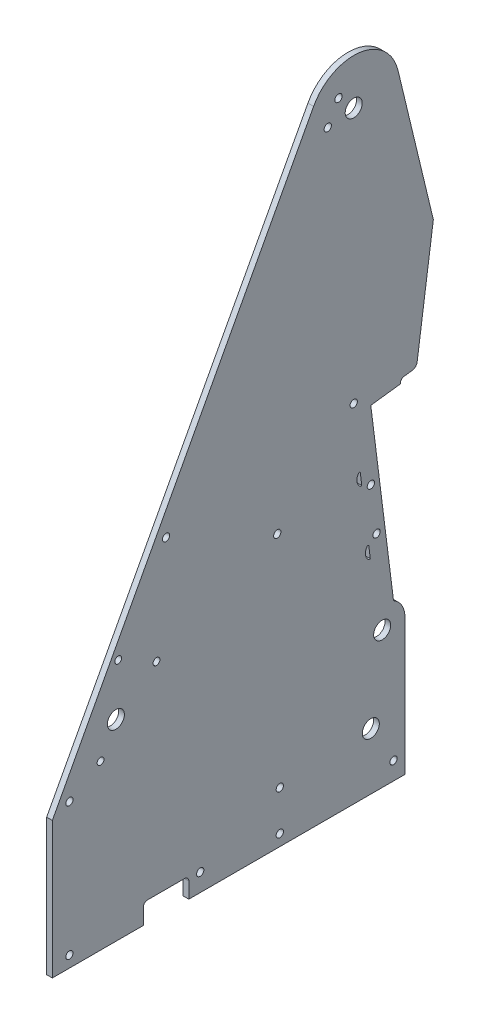
SolidWorks part; units mm, degrees
ref_plane "Front Plane" through (0, 0, 0) normal (0, 0, 1) x (1, 0, 0)
ref_plane "Top Plane" through (0, 0, 0) normal (0, 1, 0) x (1, 0, 0)
ref_plane "Right Plane" through (0, 0, 0) normal (1, 0, 0) x (0, 0, -1)
sketch "Sketch1" plane through (0, 0, 0) normal (1, 0, 0) x (0, 0, -1)
  line L0 (0, 0) -> (0, 76.2)
  line L6 (-19.05, 188.0016) -> (-2.512, 190.0852)
  line L7 (6.4943, 193.62) -> (15.875, 260.35)
  line L8 (15.875, 260.35) -> (-3.8791, 342.4892)
  line L9 (-50.965, 348.5436) -> (-196.85, 76.2)
  line L10 (-196.85, 0) -> (0, 0)
  line L11 (-196.85, 76.2) -> (-196.85, 0)
  line L12 (-19.05, 188.0016) -> (-6.35, 87.1985)
  line L13 (-0.4471, 192.7455) -> (6.4943, 193.62)
  line L14 (-2.512, 190.0852) -> (-3.1086, 194.8203) construction
  line L15 (-2.512, 190.0852) -> (6.1508, 191.1766) construction
  line L16 (6.1508, 191.1766) -> (6.4943, 193.62) construction
  arc A0 (-3.8791, 342.4892) -> (-50.965, 348.5436) centre (-28.575, 336.55) ccw
  arc A3 (0, 76.2) -> (-6.35, 87.1985) centre (-12.7, 76.2) ccw
  arc A4 (-2.512, 190.0852) -> (-0.4471, 192.7455) centre (-0.1494, 190.3829) cw
  dimension "D2" = 25.4
  dimension "D6" = 196.85
  dimension "D7" = 76.2
  dimension "D12" = 12.7
  dimension "D8" = 19.05
  dimension "D10" = 2.3813
  dimension "D1" = 28.575
  dimension "D3" = 336.55
  dimension "D4" = 25.4
  dimension "D5" = 101.6
  dimension "D9" = 6.35
  dimension ".5" = 12.7
  dimension "D11" = 76.2
  dimension "D13" = 76.2
  dimension "D14" = 15.875
  dimension "D15" = 6.35
extrude "Boss-Extrude1" add sketch "Sketch1" along normal blind 3.175
sketch "Sketch2" plane through (3.175, 0, 0) normal (1, 0, 0) x (0, 0, -1)
  line L16 (-146.05, 8.7909) -> (-146.05, -0.3034) construction
  line L17 (-123.0376, 11.1785) -> (-143.6624, 11.1785) construction
  line L18 (-120.65, -0.3034) -> (-120.65, 8.7909) construction
  line L19 (-146.05, 8.7909) -> (-146.05, 0)
  line L20 (-123.0376, 11.1785) -> (-143.6624, 11.1785)
  line L21 (-120.65, 0) -> (-120.65, 8.7909)
  line L25 (-146.05, 0) -> (-120.65, 0)
  line L26 (-196.85, 0) -> (0, 0) construction
  line L33 (-223.2996, 0) -> (-223.2996, 6.35) construction
  line L34 (-229.6496, 0) -> (-223.2996, 0) construction
  line L35 (-229.6496, 6.35) -> (-229.6496, 0) construction
  line L36 (-223.2996, 6.35) -> (-229.6496, 6.35) construction
  line L37 (-223.2996, 0) -> (-223.2996, 6.35)
  line L38 (-229.6496, 0) -> (-223.2996, 0)
  line L39 (-229.6496, 6.35) -> (-229.6496, 0)
  line L40 (-223.2996, 6.35) -> (-229.6496, 6.35)
  arc A0 (-143.6624, 11.1785) -> (-146.05, 8.7909) centre (-143.6624, 8.7909) ccw construction
  arc A1 (-120.65, 8.7909) -> (-123.0376, 11.1785) centre (-123.0376, 8.7909) ccw construction
  arc A2 (-143.6624, 11.1785) -> (-146.05, 8.7909) centre (-143.6624, 8.7909) ccw
  arc A3 (-120.65, 8.7909) -> (-123.0376, 11.1785) centre (-123.0376, 8.7909) ccw
extrude "Cut-Extrude1" cut sketch "Sketch2" against normal through all
sketch "Sketch3" plane through (3.175, 0, 0) normal (1, 0, 0) x (0, 0, -1)
  point P0 (-28.575, 336.55)
  point P4 (-12.7, 76.2)
hole_wizard "3/8 Clearance Hole1" positions "Sketch3" profile "Sketch4" hole size "3/8" standard "ANSI Inch" end condition up to next
sketch "Sketch4" plane through (3.175, 336.55, 28.575) normal (0, 1, 0) x (0, 0, -1)
  line L0 (0, 0) -> (0, 3.175)
  line L1 (0, 3.175) -> (4.7625, 3.175)
  line L2 (4.7625, 3.175) -> (4.7625, 0)
  line L5 (4.7625, 0) -> (0, 0)
  line L11 (0, -6.35) -> (0, 107.95) construction
  dimension "Thru Hole Dia." = 9.525
  dimension "Thru Hole Depth" = 3.175
sketch "Sketch5" plane through (3.175, 0, 0) normal (1, 0, 0) x (0, 0, -1)
  line L0 (-12.7, 76.2) -> (19.6681, 37.0472)
  line L1 (19.6681, 37.0472) -> (18.4836, 24.56)
  line L2 (15.6221, 41.9413) -> (-25.2806, 17.5464)
  line L3 (-15.875, 19.05) -> (-25.2806, 17.5464)
  line L4 (0, 0) -> (0, 76.2) construction
  line L5 (-15.875, 19.05) -> (-27.0501, 3.6221)
  line L6 (-27.0501, 3.6221) -> (-54.7505, 169.5016)
  line L7 (50.8, 0) -> (50.8, 73.5762) construction
  dimension "D1" = 44.45
  dimension "D2" = 50.8
  dimension "D3" = 45
  dimension "D4" = 60.325
  dimension "D5" = 19.05
  dimension "D6" = 15.875
  dimension "D7" = 9.525
  dimension "D8" = 47.625
  dimension "D9" = 19.05
  dimension "D10" = 45
  dimension "D11" = 50.8
sketch "Sketch6" plane through (3.175, 0, 0) normal (1, 0, 0) x (0, 0, -1)
  circle A3 centre (-161.3885, 107.3015) radius 4.7625
  circle A5 centre (-161.3885, 107.3015) radius 6.985 construction
  circle A8 centre (-160.0862, 135.4185) radius 1.905 construction
  circle A9 centre (-138.7037, 123.9646) radius 1.905 construction
  arc A10 (-168.2338, 90.4891) -> (-169.0344, 93.0278) centre (-169.9339, 91.3486) ccw construction
  arc A11 (-169.0344, 93.0278) -> (-171.5914, 92.2876) centre (-169.9339, 91.3486) ccw construction
  arc A12 (-171.5914, 92.2876) -> (-168.2338, 90.4891) centre (-169.9339, 91.3486) ccw construction
  circle A17 centre (-160.0862, 135.4185) radius 1.905
  circle A18 centre (-138.7037, 123.9646) radius 1.905
  arc A19 (-168.2338, 90.4891) -> (-169.0344, 93.0278) centre (-169.9339, 91.3486) ccw
  arc A20 (-169.0344, 93.0278) -> (-171.5914, 92.2876) centre (-169.9339, 91.3486) ccw
  arc A21 (-171.5914, 92.2876) -> (-168.2338, 90.4891) centre (-169.9339, 91.3486) ccw
  dimension "D1" = 9.525
extrude "Cut-Extrude2" cut sketch "Sketch6" against normal through all
sketch "Sketch10" plane through (3.175, 0, 0) normal (1, 0, 0) x (0, 0, -1)
  circle A0 centre (-71.2566, 151.9429) radius 2.032
  dimension "D1" = 4.064
extrude "Cut-Extrude4" cut sketch "Sketch10" against normal through all
sketch "Sketch11" plane through (3.175, 0, 0) normal (1, 0, 0) x (0, 0, -1)
  circle A0 centre (-187.325, 80.5336) radius 2.032
  circle A1 centre (-187.325, 6.35) radius 2.032
  circle A2 centre (-187.325, 6.35) radius 2.032 construction
  circle A3 centre (-187.325, 80.5336) radius 2.032 construction
  dimension "D1" = 4.064
extrude "Cut-Extrude5" cut sketch "Sketch11" against normal through all
sketch "Sketch13" plane through (0, 0, 0) normal (-1, 0, 0) x (0, 0, 1)
  circle A0 centre (37.0603, 345.5883) radius 2.032
  circle A1 centre (43.057, 334.3933) radius 2.032
  circle A2 centre (37.0603, 345.5883) radius 1.905 construction
  circle A3 centre (43.057, 334.3933) radius 1.905 construction
  dimension "D1" = 4.064
extrude "Cut-Extrude6" cut sketch "Sketch13" against normal through all
sketch "Sketch14" plane through (3.175, 0, 0) normal (1, 0, 0) x (0, 0, -1)
  line L0 (-50.965, 348.5436) -> (-196.85, 76.2) construction
  line L1 (-133.35, 181.2962) -> (-138.9475, 184.2946) construction
  circle A0 centre (-133.35, 181.2962) radius 2.032
  dimension "D1" = 4.064
  dimension "D2" = 6.35
  dimension "D3" = 133.35
extrude "Cut-Extrude7" cut sketch "Sketch14" against normal through all
sketch "Sketch15" plane through (3.175, 0, 0) normal (1, 0, 0) x (0, 0, -1)
  circle A0 centre (-19.05, 31.75) radius 4.7625
  circle A1 centre (-12.7, 76.2) radius 4.7625 construction
  circle A2 centre (-28.575, 193.675) radius 2.032
  dimension "D1" = 44.45
  dimension "D3" = 4.064
  dimension "D2" = 6.35
  dimension "D4" = 161.925
  dimension "D5" = 9.525
extrude "Cut-Extrude8" cut sketch "Sketch15" against normal through all
sketch "Sketch16" plane through (3.175, 0, 0) normal (1, 0, 0) x (0, 0, -1)
  line L0 (-24.978, 158.8539) -> (-24.0851, 151.7662)
  line L1 (-6.35, 87.1985) -> (-19.05, 188.0016) construction
  line L2 (-20.2155, 121.0527) -> (-21.0031, 120.9535)
  line L3 (-24.978, 158.8539) -> (-25.7656, 158.7547)
  line L4 (-24.0851, 151.7662) -> (-24.8726, 151.667)
  line L5 (-12.7, 137.6001) -> (-26.6484, 135.8427) construction
  line L6 (-19.3226, 113.965) -> (-20.1101, 113.8658)
  line L7 (-19.3226, 113.965) -> (-20.2155, 121.0527)
  line L8 (-25.3253, 161.6102) -> (-23.7378, 149.0099) construction
  arc A0 (-25.7656, 158.7547) -> (-24.8726, 151.667) centre (-21.7352, 155.6624) ccw
  arc A1 (-20.1101, 113.8658) -> (-21.0031, 120.9535) centre (-16.9727, 117.8612) cw
  circle A2 centre (-19.0126, 149.6052) radius 2.032
  circle A3 centre (-15.8376, 124.4044) radius 2.032
  point P2 (-24.5315, 155.31)
  dimension "D2" = 0.7937
  dimension "D3" = 5.08
  dimension "D5" = 4.064
  dimension "D1" = 7.1437
  dimension "D4" = 38.1
  dimension "D6" = 4.7625
  dimension "D7" = 25.4
extrude "Cut-Extrude9" cut sketch "Sketch16" against normal up to next
fillet "Fillet1" radius 3.175 1 edges at (1.5875, 193.62, -6.4943)
sketch "Sketch17" plane through (3.175, 0, 0) normal (1, 0, 0) x (0, 0, -1)
  circle A0 centre (-6.35, 9.9085) radius 2.032
  circle A1 centre (-69.85, 6.35) radius 2.032
  circle A2 centre (-114.3, 9.9085) radius 2.032
  circle A3 centre (-114.3, 9.9085) radius 1.905 construction
  circle A4 centre (-69.85, 6.35) radius 2.286 construction
  circle A5 centre (-6.35, 9.9085) radius 1.905 construction
  circle A6 centre (-69.85, 28.575) radius 2.032
  circle A7 centre (-69.85, 28.575) radius 1.905 construction
  dimension "D1" = 4.064
extrude "Cut-Extrude10" cut sketch "Sketch17" against normal through all
